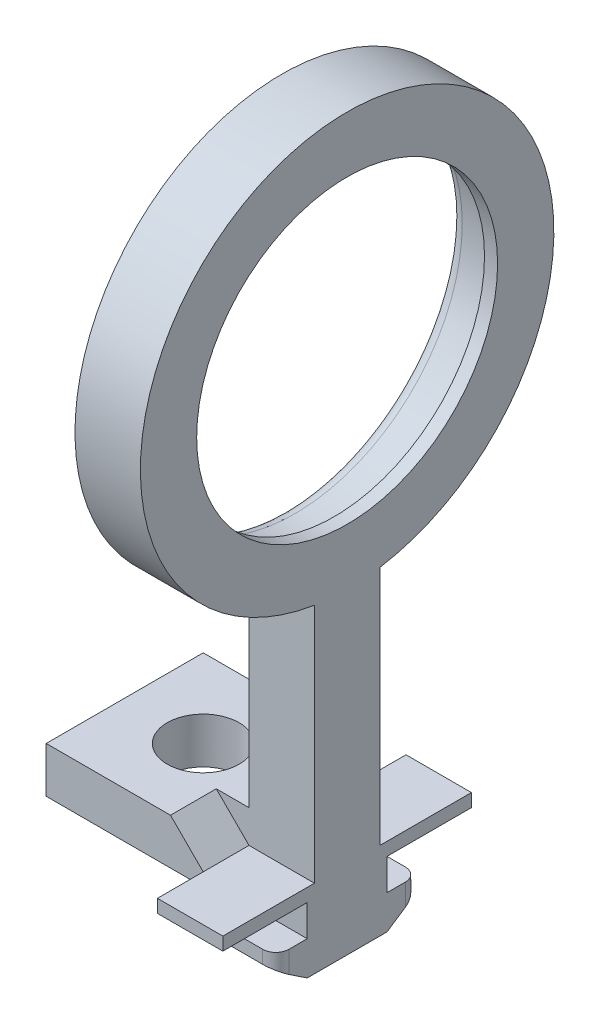
SolidWorks part; units mm, degrees
ref_plane "Front Plane" through (0, 0, 0) normal (0, 0, 1) x (1, 0, 0)
ref_plane "Top Plane" through (0, 0, 0) normal (0, 1, 0) x (1, 0, 0)
ref_plane "Right Plane" through (0, 0, 0) normal (1, 0, 0) x (0, 0, -1)
sketch "Sketch1" plane through (0, 0, 0) normal (1, 0, 0) x (0, 0, -1)
  line L0 (12.8, 0) -> (15.8, 0)
  line L1 (12.8, 0) -> (12.5, 0)
  line L2 (12.5, 0) -> (11.5, 0) construction
  circle A0 centre (0, 0) radius 12.5 construction
  circle A1 centre (0, 0) radius 12.8
  circle A2 centre (0, 0) radius 15.8
  circle A4 centre (0, 0) radius 12.5 construction
  circle A5 centre (0, 0) radius 11.5
  dimension "D3" = 1
  dimension "D1" = 3
  dimension "D2" = 0.3
extrude "Boss-Extrude1" add sketch "Sketch1" against normal blind 5 contours A2 A1 region at (0, 0, 15.3531)
sketch "Sketch2" plane through (0, 0, 0) normal (1, 0, 0) x (0, 0, -1)
  line L0 (0, -15.8) -> (0, -35) construction
  line L5 (-2.5, -35) -> (2.5, -35)
  line L6 (2.5, -35) -> (2.5, -15.601)
  line L7 (-2.5, -35) -> (-2.5, -15.601)
  line L8 (2.5, -25.3005) -> (-2.5, -25.3005) construction
  line L9 (-2.5, -15.601) -> (2.5, -15.601)
  circle A0 centre (0, 0) radius 15.8 construction
  circle A1 centre (0, 0) radius 15.8 construction
  point P10 (0, -35)
  dimension "D1" = 5
extrude "Boss-Extrude2" add sketch "Sketch2" against normal blind 5
sketch "Sketch3" plane through (0, 0, 0) normal (1, 0, 0) x (0, 0, -1)
  line L1 (-2.5, -35) -> (2.5, -35) construction
  line B0 (0, -40) -> (0, -35) construction
  line B1 (-9.5, -35) -> (-9.5, -34)
  line B2 (-3.05, -35) -> (3.05, -35) construction
  line B3 (-3.05, -35) -> (-3.05, -37.4)
  line B4 (3.05, -35) -> (3.05, -37.4)
  line B5 (-3.05, -37.4) -> (-5.45, -37.4)
  line B6 (-5.45, -37.4) -> (-5.45, -38.4)
  line B7 (3.05, -37.4) -> (5.45, -37.4)
  line B8 (5.45, -37.4) -> (5.45, -38.4)
  line B9 (-3.05, -35) -> (-9.5, -35)
  line B10 (-9.5, -34) -> (9.5, -34)
  line B11 (3.05, -35) -> (9.5, -35)
  line B12 (9.5, -34) -> (9.5, -35)
  line B13 (-3.05, -37.4) -> (-3.05, -40) construction
  line B14 (-5.45, -38.4) -> (-3.05, -40)
  line B15 (3.05, -37.4) -> (3.05, -40) construction
  line B16 (5.45, -38.4) -> (3.05, -40)
  line B17 (3.05, -40) -> (-3.05, -40)
sketch_block_instance "Block-2020 rail insert-1"
sketch_block "Block-2020 rail insert" parameters "D1"=5, "D2"=6.1, "D3"=2.4, "D4"=2.4, "D5"=1, "D6"=1, "D7"=19
extrude "Boss-Extrude3" add sketch "Sketch3" against normal blind 5
fillet "Fillet1" radius 1 2 edges at (0, -37.9, 5.45) (0, -37.9, -5.45)
sketch "Sketch38" plane through (-5, 0, 0) normal (-1, 0, 0) x (0, 0, 1)
  line L0 (2.5, -33.25) -> (-2.5, -33.25) construction
  line L1 (2.5, -15.601) -> (2.5, -34) construction
  line L2 (-2.5, -34) -> (-2.5, -15.601) construction
  line L3 (-6, -31.5) -> (6, -31.5)
  line L4 (-6, -31.5) -> (-6, -35)
  line L5 (-6, -35) -> (6, -35)
  line L6 (6, -31.5) -> (6, -35)
  line L7 (-6, -31.5) -> (6, -35) construction
  line L8 (-6, -35) -> (6, -31.5) construction
  dimension "D1" = 12
  dimension "D2" = 3.5
extrude "Boss-Extrude28" add sketch "Sketch38" along normal blind 12
sketch "Sketch39" plane through (0, -31.5, 0) normal (0, 1, 0) x (1, 0, 0)
  line L0 (-17, -6) -> (-5, 6) construction
  circle A0 centre (-11, 0) radius 2.75
  dimension "D1" = 5.5
extrude "Cut-Extrude3" cut sketch "Sketch39" against normal up to next contours A0
chamfer "Chamfer1" distance 2.5 angle 45 2 edges at (-5, -31.5, 4.25) (-5, -31.5, -4.25)
fillet "Fillet3" radius 1 1 edges at (-5, 0, -12.8)
ref_axis "Axis1" through (0, -35, 0) along (1, 0, 0)
extrude "Boss-Extrude29" add sketch "Sketch1<3>" against normal blind 1 contours A1 A5 region at (0, 0, 12.438)
sketch "Sketch1<3>" plane through (0, 0, 0) normal (1, 0, 0) x (0, 0, -1) same geometry as "Sketch1"
